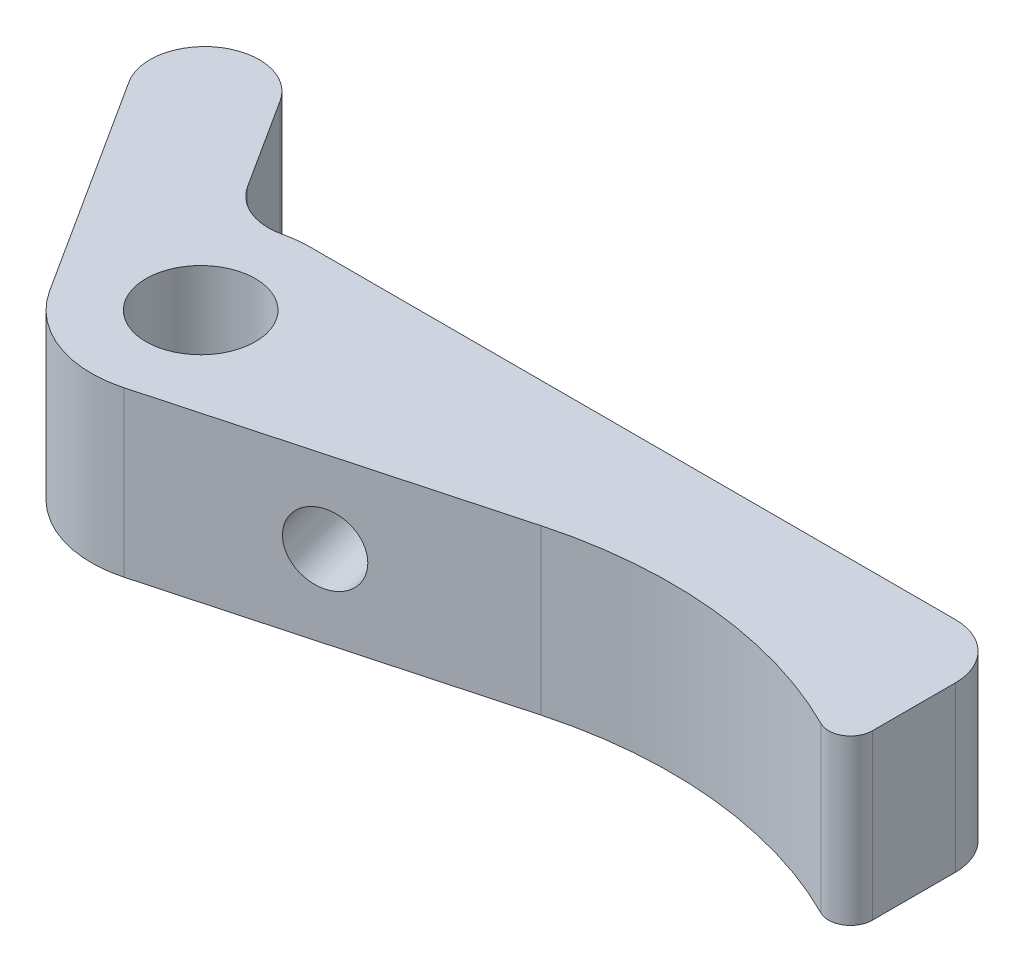
SolidWorks part; units mm, degrees
material "6061-T6 (SS)"
ref_plane "Front" through (0, 0, 0) normal (0, 0, 1) x (1, 0, 0)
ref_plane "Top" through (0, 0, 0) normal (0, 1, 0) x (1, 0, 0)
ref_plane "Right" through (0, 0, 0) normal (1, 0, 0) x (0, 0, -1)
sketch "Sketch1" plane through (0, 0, 0) normal (0, 1, 0) x (1, 0, 0)
  line L0 (0, 6.35) -> (40.64, 6.35)
  line L1 (40.64, 6.35) -> (40.64, -3.81)
  line L2 (1.664, -6.1281) -> (20.714, -0.9554)
  line L3 (-3.4246, 5.3474) -> (-9.9315, 15.5074)
  line L4 (-9.9315, 15.5074) -> (-15.2788, 12.0827)
  line L5 (-15.2788, 12.0827) -> (-5.3474, -3.4246)
  circle A0 centre (0, 0) radius 3.175
  circle A1 centre (0, 0) radius 6.35
  arc A2 (20.714, -0.9554) -> (40.64, -3.81) centre (27.3699, -25.4679) cw
  dimension "D1" = 6.35
  dimension "D2" = 12.7
  dimension "D5" = 19.05
  dimension "D7" = 12.065
  dimension "D6" = 25.4
  dimension "D3" = 40.64
  dimension "D4" = 10.16
  dimension "D8" = 6.35
  dimension "D9" = 10.16
extrude "Boss-Extrude1" add sketch "Sketch1" along normal blind 9.525 contours A1 A0 | L2 A2 L1 L0 A1 | A1 L3 L4 L5 region at (21.7984, 0, -2.1451) region at (4.3631, 0, -4.3631) region at (-9.094, 0, -7.9821)
fillet "Fillet1" radius 3.175 4 edges at (40.64, 4.7625, -6.35) (-3.4246, 4.7625, -5.3474) (-15.2788, 4.7625, -12.0827) (-9.9315, 4.7625, -15.5074)
fillet "Fillet2" radius 1.27 1 edges at (40.64, 4.7625, 3.81)
sketch "Sketch4" plane through (1.664, 0, 6.1281) normal (0.262, 0, 0.9651) x (0.9651, 0, -0.262)
  line L0 (0, 4.7625) -> (9.525, 4.7625) construction
  line L1 (0, 9.525) -> (0, 0) construction
  point P0 (9.525, 4.7625)
  dimension "D1" = 9.525
hole_wizard "#10-32 Tapped Hole2" positions "Sketch4" profile "Sketch3" tap size "#10-32" standard "ANSI Inch"
sketch "Sketch3" plane through (10.8561, 4.7625, 3.6322) normal (0, 1, 0) x (0.9651, 0, -0.262)
  line L0 (0, 0) -> (0, 7.5633)
  line L1 (0, 7.5633) -> (2.0193, 6.35)
  line L2 (2.0193, 6.35) -> (2.0193, 0)
  line L5 (2.0193, 0) -> (0, 0)
  line L10 (0, 7.5633) -> (-2.0193, 6.35) construction
  line L11 (0, -6.35) -> (0, 107.95) construction
  dimension "Tap Drill Dia." = 4.0386
  dimension "Tap Drill Depth" = 6.35
  dimension "Drill Angle" = 118
cosmetic thread "Hole Thread1" parameters "D1"=9.652, "D2"=4.826
